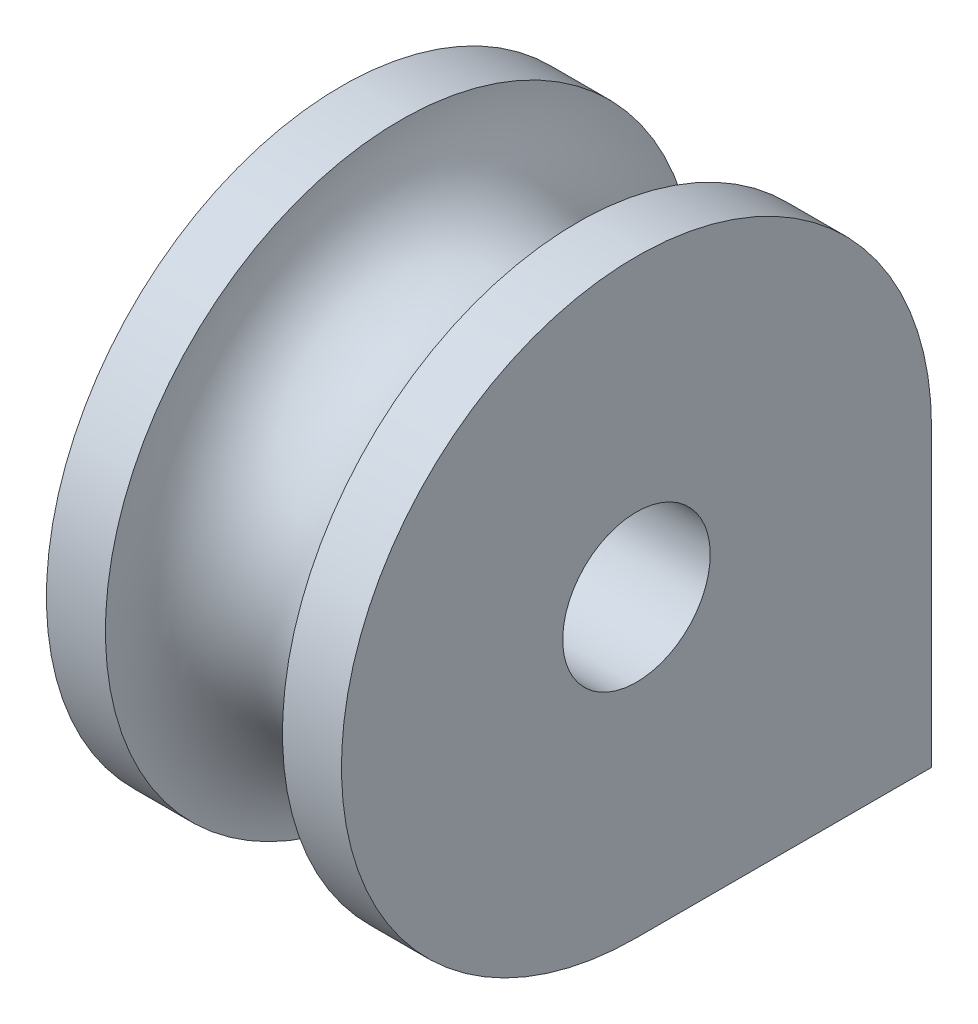
SolidWorks part; units mm, degrees
ref_plane "Front Plane" through (0, 0, 0) normal (0, 0, 1) x (1, 0, 0)
ref_plane "Top Plane" through (0, 0, 0) normal (0, 1, 0) x (1, 0, 0)
ref_plane "Right Plane" through (0, 0, 0) normal (1, 0, 0) x (0, 0, -1)
sketch "Sketch1" plane through (0, 0, 0) normal (0, 1, 0) x (1, 0, 0)
  line L0 (15, 50) -> (25, 50)
  line L1 (-25, 0) -> (25, 0)
  line L2 (-25, 0) -> (-25, 50)
  line L3 (-25, 50) -> (-15, 50)
  line L4 (25, 0) -> (25, 50)
  line L5 (-25, 0) -> (25, 50) construction
  line L6 (-25, 50) -> (25, 0) construction
  line L7 (0, 50) -> (0, 0) construction
  arc A0 (-15, 50) -> (15, 50) centre (0, 50) ccw
  point P0 (0, 0)
  point P7 (0, 0)
  point P11 (0, 0)
  point P13 (0, 0)
  point P14 (0, 0)
  dimension "D2" = 30
  dimension "D1" = 50
  dimension "D3" = 50
revolve "Revolve1" add sketch "Sketch1" angle 270 about L1
extrude "Boss-Extrude1" add sketch "Sketch1<2>" against normal up to vertex (50 mm away) up to point (-15, -50, 0)
sketch "Sketch1<2>" plane through (0, 0, 0) normal (0, 1, 0) x (1, 0, 0) same geometry as "Sketch1"
sketch "Sketch3" plane through (25, 0, 0) normal (1, 0, 0) x (0, 0, -1)
  circle A0 centre (0, 0) radius 12.5
  dimension "D1" = 25
extrude "Cut-Extrude2" cut sketch "Sketch3" against normal through all
